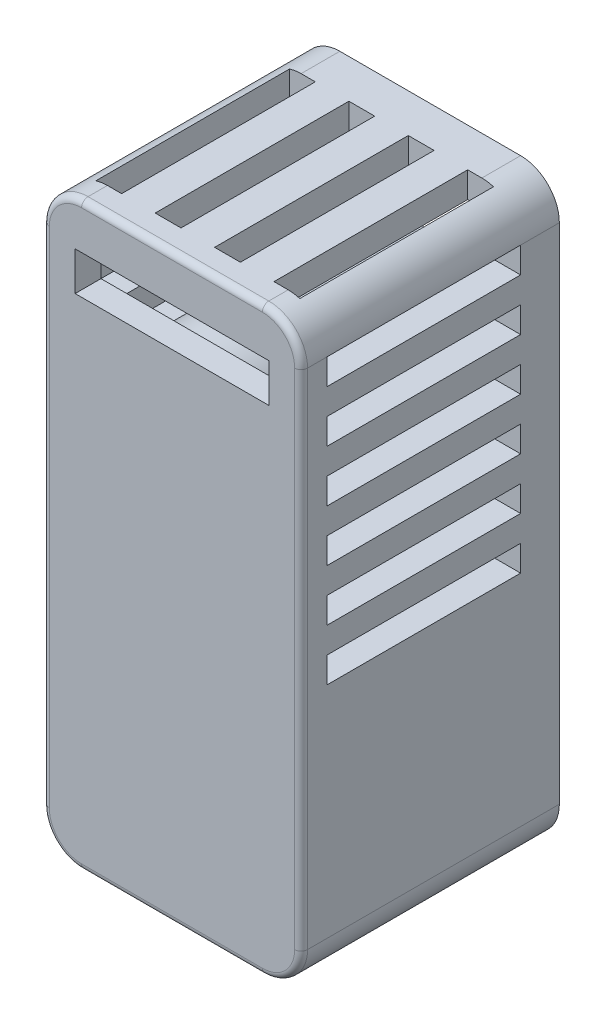
SolidWorks part; units mm, degrees
ref_plane "Front Plane" through (0, 0, 0) normal (0, 0, 1) x (1, 0, 0)
ref_plane "Top Plane" through (0, 0, 0) normal (0, 1, 0) x (1, 0, 0)
ref_plane "Right Plane" through (0, 0, 0) normal (1, 0, 0) x (0, 0, -1)
sketch "Sketch2" plane through (0, 0, 0) normal (0, 0, 1) x (1, 0, 0)
  line L1 (10, -22.5) -> (-10, -22.5)
  line L2 (10, -22.5) -> (10, 22.5)
  line L3 (10, 22.5) -> (-10, 22.5)
  line L4 (-10, -22.5) -> (-10, 22.5)
  line L5 (10, -22.5) -> (-10, 22.5) construction
  line L6 (10, 22.5) -> (-10, -22.5) construction
  point P0 (0, 0)
  dimension "D1" = 20
  dimension "D2" = 45
extrude "Boss-Extrude1" add sketch "Sketch2" along normal blind 20
shell "Shell1" thickness 2 removed face at (0, 0, 0)
sketch "Sketch3" plane through (10, 0, 0) normal (1, 0, 0) x (0, 0, -1)
  line L0 (-20, 22.5) -> (0, 22.5) construction
  line L1 (-18, 19.5) -> (-3, 19.5)
  line L2 (-18, 19.5) -> (-18, 17.5)
  line L3 (-18, 17.5) -> (-3, 17.5)
  line L4 (-3, 19.5) -> (-3, 17.5)
  line L5 (-20, -22.5) -> (-20, 22.5) construction
  line L6 (0, 11) -> (0, -11) construction
  line L7 (-18, 15.5) -> (-3, 15.5)
  line L8 (-18, 15.5) -> (-18, 13.5)
  line L9 (-18, 13.5) -> (-3, 13.5)
  line L10 (-3, 15.5) -> (-3, 13.5)
  line L11 (-18, 11.5) -> (-3, 11.5)
  line L12 (-18, 11.5) -> (-18, 9.5)
  line L13 (-18, 9.5) -> (-3, 9.5)
  line L14 (-3, 11.5) -> (-3, 9.5)
  line L15 (-18, 7.5) -> (-3, 7.5)
  line L16 (-18, 7.5) -> (-18, 5.5)
  line L17 (-18, 5.5) -> (-3, 5.5)
  line L18 (-3, 7.5) -> (-3, 5.5)
  line L19 (-18, 3.5) -> (-3, 3.5)
  line L20 (-18, 3.5) -> (-18, 1.5)
  line L21 (-18, 1.5) -> (-3, 1.5)
  line L22 (-3, 3.5) -> (-3, 1.5)
  line L23 (-18, -0.5) -> (-3, -0.5)
  line L24 (-18, -0.5) -> (-18, -2.5)
  line L25 (-18, -2.5) -> (-3, -2.5)
  line L26 (-3, -0.5) -> (-3, -2.5)
  dimension "D1" = 3
  dimension "D2" = 2
  dimension "D3" = 3
  dimension "D4" = 2
  dimension "D5" = 6
extrude "Cut-Extrude1" cut sketch "Sketch3" against normal up to surface (20 mm away) up to face at (-10, 0, 10)
sketch "Sketch4" plane through (0, 22.5, 0) normal (0, 1, 0) x (1, 0, 0)
  line L0 (10, -20) -> (-10, -20) construction
  line L1 (-7.9, -3) -> (-5.9, -3)
  line L2 (-7.9, -3) -> (-7.9, -18)
  line L3 (-7.9, -18) -> (-5.9, -18)
  line L4 (-5.9, -3) -> (-5.9, -18)
  line L5 (-11, 0) -> (11, 0) construction
  line L6 (-3.3, -3) -> (-1.3, -3)
  line L7 (-3.3, -3) -> (-3.3, -18)
  line L8 (-3.3, -18) -> (-1.3, -18)
  line L9 (-1.3, -3) -> (-1.3, -18)
  line L10 (1.3, -3) -> (3.3, -3)
  line L11 (1.3, -3) -> (1.3, -18)
  line L12 (1.3, -18) -> (3.3, -18)
  line L13 (3.3, -3) -> (3.3, -18)
  line L14 (5.9, -3) -> (7.9, -3)
  line L15 (5.9, -3) -> (5.9, -18)
  line L16 (5.9, -18) -> (7.9, -18)
  line L17 (7.9, -3) -> (7.9, -18)
  line L18 (-10, -20) -> (-10, 0) construction
  dimension "D1" = 2
  dimension "D2" = 3
  dimension "D3" = 2
  dimension "D5" = 2.1
  dimension "D4" = 4
extrude "Cut-Extrude2" cut sketch "Sketch4" against normal up to next
fillet "Fillet1" radius 3 4 edges at (10, -22.5, 10) (-10, -22.5, 10) (-10, 22.5, 10) (10, 22.5, 10)
sketch "Sketch7" plane through (0, 0, 20) normal (0, 0, 1) x (1, 0, 0)
  line L5 (0, -11) -> (0, 11) construction
  line L6 (7.5, 16) -> (-7.5, 16)
  line L10 (7.5, 16) -> (7.5, 19)
  line L11 (7.5, 19) -> (-7.5, 19)
  line L16 (-7.5, 16) -> (-7.5, 19)
  line L17 (7.5, 16) -> (-7.5, 19) construction
  line L30 (7.5, 19) -> (-7.5, 16) construction
  line L31 (7, 22.5) -> (-7, 22.5) construction
  point P0 (0, 17.5)
  dimension "D1" = 3
  dimension "D2" = 15
  dimension "D3" = 5
extrude "Cut-Extrude3" cut sketch "Sketch7" against normal up to surface (2 mm away)
fillet "Fillet3" radius 0.5 8 edges at (9.1213, 21.6213, 20) (0, 22.5, 20) (-9.1213, 21.6213, 20) (-10, 0, 20) (-9.1213, -21.6213, 20) (0, -22.5, 20) (9.1213, -21.6213, 20) (10, 0, 20)
sketch "Sketch8" plane through (0, 0, 18) normal (0, 0, -1) x (-1, 0, 0)
  line L0 (-8, 20.5) -> (8, 20.5) construction
  circle A0 centre (0, 10.5) radius 2.8
  circle A1 centre (0, 10.5) radius 5.2
  dimension "D1" = 2.4
  dimension "D2" = 10
extrude "Boss-Extrude2" add sketch "Sketch8" along normal blind 16.4 contours A1 A0 | A0 | A0 | A1 region at (0, 10.5, 18) region at (5.0529, 10.5, 18)
hole_wizard "CBORE for M5 Hex Head Bolt1" positions "3DSketch1" profile "Sketch9" counterbore size "M5" standard "ANSI Metric"
sketch3d "3DSketch1"
  line L0 (0, 10.5, 1.6) -> (0, 10.5, 18) construction
  point P0 (0, 10.5, 1.6)
sketch "Sketch9" plane through (0, 10.5, 1.6) normal (1, 0, 0) x (0, 1, 0)
  line L0 (0, 0) -> (0, 6.5923)
  line L1 (0, 6.5923) -> (2.65, 5)
  line L2 (2.65, 5) -> (2.65, 3)
  line L3 (2.65, 3) -> (3.25, 3)
  line L4 (3.25, 3) -> (3.25, 0)
  line L5 (3.25, 0) -> (0, 0)
  line L10 (0, 6.5923) -> (-2.65, 5) construction
  line L11 (0, -6.35) -> (0, 107.95) construction
  dimension "Hole Dia." = 5.3
  dimension "Hole Depth" = 5
  dimension "C'Bore Dia." = 6.5
  dimension "C'Bore Depth" = 3
  dimension "Drill Angle" = 118
